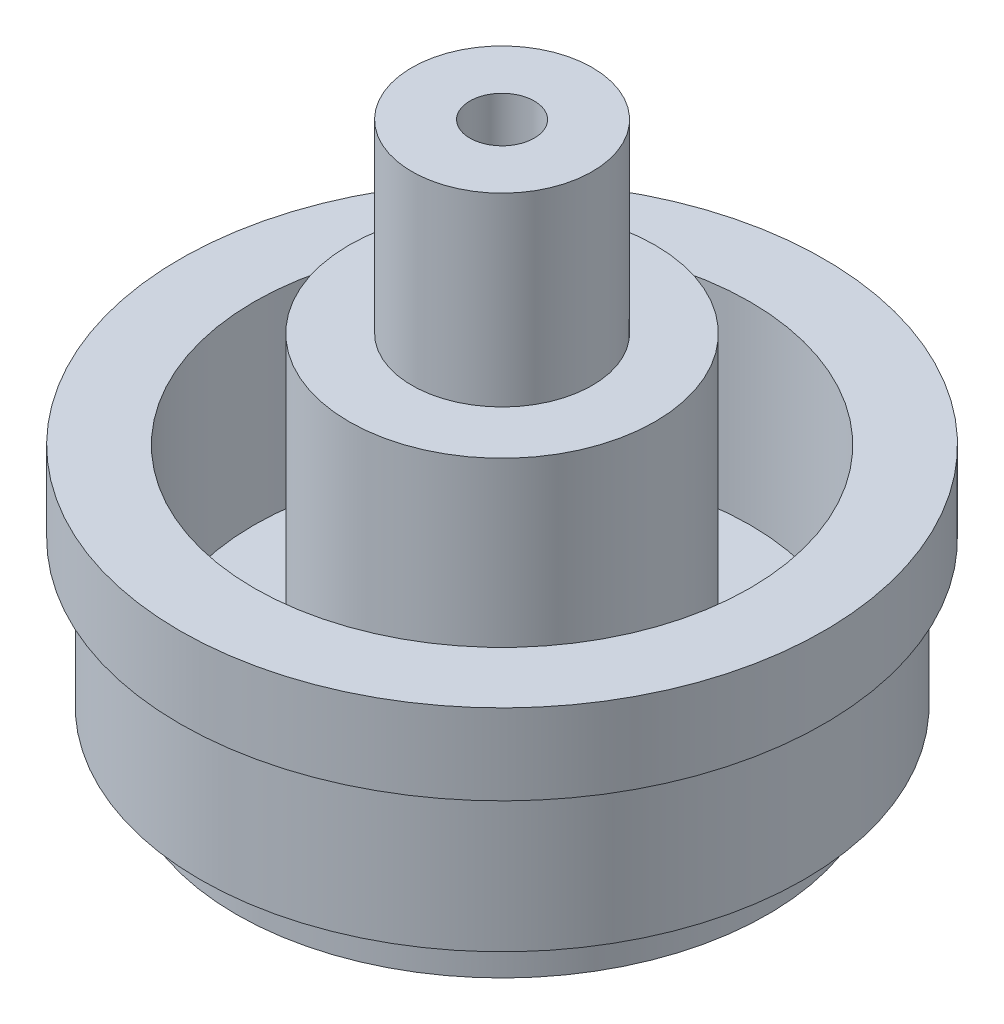
SolidWorks part; units mm, degrees
ref_plane "Front Plane" through (0, 0, 0) normal (0, 0, 1) x (1, 0, 0)
ref_plane "Top Plane" through (0, 0, 0) normal (0, 1, 0) x (1, 0, 0)
ref_plane "Right Plane" through (0, 0, 0) normal (1, 0, 0) x (0, 0, -1)
sketch "Sketch1" plane through (0, 0, 0) normal (0, 1, 0) x (1, 0, 0)
  circle A0 centre (0, 0) radius 50.8
  circle A1 centre (0, 0) radius 39.116
  dimension "D1" = 101.6
  dimension "D2" = 78.232
extrude "Boss-Extrude1" add sketch "Sketch1" against normal blind 12.7
ref_plane "Plane4" through (0, -15.24, 0) normal (0, -1, 0) x (-1, 0, 0)
sketch "Sketch2" plane through (0, -15.24, 0) normal (0, -1, 0) x (-1, 0, 0)
  circle A0 centre (0, 0) radius 47.625
  circle A1 centre (0, 0) radius 39.116
  dimension "D1" = 95.25
  dimension "D2" = 78.232
extrude "Boss-Extrude2" add sketch "Sketch2" against normal up to surface (2.54 mm away) and the other way blind 20.32 separate body up to face at (0, -12.7, 39.116)
ref_plane "Plane5" through (0, -38.1, 0) normal (0, 1, 0) x (1, 0, 0)
sketch "Sketch4" plane through (0, -38.1, 0) normal (0, 1, 0) x (1, 0, 0)
  circle A0 centre (0, 0) radius 41.91
  dimension "D1" = 83.82
extrude "Boss-Extrude3" add sketch "Sketch4" along normal offset from surface 30.48 and the other way blind 5.08 separate body up to face at (0, 0, 39.116)
ref_plane "Plane6" through (0, -27.94, 0) normal (0, 1, 0) x (1, 0, 0)
sketch "Sketch5" plane through (0, -27.94, 0) normal (0, 1, 0) x (1, 0, 0)
  circle A0 centre (0, 0) radius 24.13
  dimension "D1" = 48.26
extrude "Boss-Extrude4" add sketch "Sketch5" along normal blind 43.18
ref_plane "Plane7" through (0, 17.78, 0) normal (0, 1, 0) x (1, 0, 0)
sketch "Sketch6" plane through (0, 17.78, 0) normal (0, 1, 0) x (1, 0, 0)
  circle A0 centre (0, 0) radius 14.224
  dimension "D1" = 28.448
extrude "Boss-Extrude5" add sketch "Sketch6" along normal blind 29.21 from surface separate body starting at face at (0, 15.24, 24.13)
ref_plane "Plane8" through (0, -45.72, 0) normal (0, -1, 0) x (-1, 0, 0)
sketch "Sketch7" plane through (0, -45.72, 0) normal (0, -1, 0) x (-1, 0, 0)
  circle A0 centre (0, 0) radius 16.51
  dimension "D1" = 33.02
extrude "Cut-Extrude1" cut sketch "Sketch7" against normal blind 50.8
ref_plane "Plane9" through (0, 46.99, 0) normal (0, 1, 0) x (1, 0, 0)
sketch "Sketch8" plane through (0, 46.99, 0) normal (0, 1, 0) x (1, 0, 0)
  circle A0 centre (0, 0) radius 5.08
  dimension "D1" = 10.16
extrude "Cut-Extrude2" cut sketch "Sketch8" against normal blind 26.416
